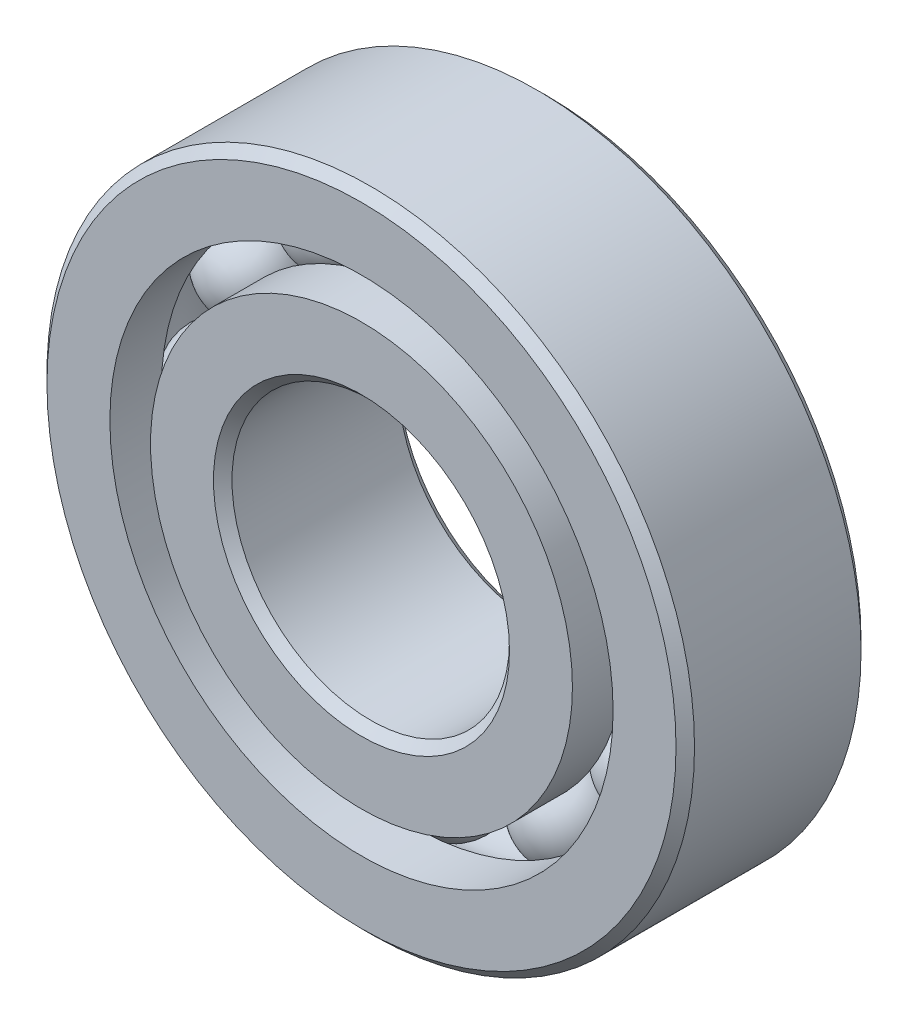
SolidWorks part; units mm, degrees
ref_plane "Front Plane" through (0, 0, 0) normal (0, 0, 1) x (1, 0, 0)
ref_plane "Top Plane" through (0, 0, 0) normal (0, 1, 0) x (1, 0, 0)
ref_plane "Right Plane" through (0, 0, 0) normal (1, 0, 0) x (0, 0, -1)
sketch "Sketch1" plane through (0, 0, 0) normal (1, 0, 0) x (0, 0, -1)
  line L0 (-4, 0) -> (4, 0) construction
  line L1 (0, 14) -> (0, -14) construction
  line L2 (3.6, 14) -> (-3.6, 14)
  line L3 (-3.6, 14) -> (-4, 13.6)
  line L4 (-4, 13.6) -> (-4, 10.8791)
  line L5 (-4, 10.8791) -> (-1.7778, 10.8791)
  line L6 (4, 10.8791) -> (1.7778, 10.8791)
  line L7 (4, 13.6) -> (4, 10.8791)
  line L8 (3.6, 14) -> (4, 13.6)
  line L9 (0, 14) -> (0, 10) construction
  line L10 (0, 10) -> (0, 6) construction
  arc A0 (-1.7778, 10.8791) -> (1.7778, 10.8791) centre (0, 10) cw
  point P14 (0, 6)
  dimension "Width" = 8
  dimension "OD" = 28
  dimension "D1" = 45
  dimension "D2" = 0.4
  dimension "Shaft Dia" = 12
  dimension "D3" = 3.5556
  dimension "D4" = 0.8791
revolve "Revolve1" add sketch "Sketch1" angle 360 about L0
sketch "Sketch3" plane through (0, 0, 0) normal (1, 0, 0) x (0, 0, -1)
  line L0 (-4, 9.1209) -> (-1.7778, 9.1209)
  line L1 (0, 14) -> (0, -14) construction
  line L2 (-4, 13.6) -> (-4, 10.8791) construction
  line L3 (-4, 9.1209) -> (-4, 6.4)
  line L4 (-3.6, 14) -> (-4, 13.6) construction
  line L5 (-4, 6.4) -> (-3.6, 6)
  line L6 (-3.6, 6) -> (3.6, 6)
  line L7 (3.6, 14) -> (3.6, -14) construction
  line L8 (3.6, 6) -> (4, 6.4)
  line L9 (4, -13.6) -> (4, 13.6) construction
  line L10 (4, 6.4) -> (4, 9.1209)
  line L11 (4, 9.1209) -> (1.7778, 9.1209)
  line L13 (3.6, 14) -> (4, 13.6) construction
  arc A0 (1.7778, 10.8791) -> (-1.7778, 10.8791) centre (0, 10) ccw construction
  arc A1 (1.7778, 9.1209) -> (-1.7778, 9.1209) centre (0, 10) cw
revolve "Revolve3" add sketch "Sketch3" angle 360 about L0
sketch "Sketch4" plane through (0, 0, 0) normal (1, 0, 0) x (0, 0, -1)
  line L0 (-1.9833, 10) -> (1.9833, 10)
  arc A2 (-1.9833, 10) -> (1.9833, 10) centre (0, 10) cw
  arc A3 (1.7778, 10.8791) -> (-1.7778, 10.8791) centre (0, 10) ccw construction
revolve "Revolve4" add sketch "Sketch4" angle 360 about L0
ref_axis "Axis1" through (0, 0, -4) along (0, 0, 1)
pattern_circular "CirPattern1" count 12 every 30 about axis through (0, 0, -4) along (0, 0, 1) of bodies 104
sketch "Sketch5" plane through (0, 0, 0) normal (1, 0, 0) x (0, 0, -1)
  line L0 (-4, 10.8791) -> (-1.7778, 10.8791) construction
  line L1 (-3.8, 10.8791) -> (-1.9833, 10.8791)
  line L2 (-3.8, 10.8791) -> (-3.8, 9.1209)
  line L3 (-3.8, 9.1209) -> (-1.9833, 9.1209)
  line L4 (-1.9833, 10.8791) -> (-1.9833, 9.1209)
  line L5 (-4, 9.1209) -> (-1.7778, 9.1209) construction
  line L6 (4, 10.8791) -> (1.7778, 10.8791) construction
  line L7 (3.8, 10.8791) -> (1.9833, 10.8791)
  line L8 (3.8, 10.8791) -> (3.8, 9.1209)
  line L9 (3.8, 9.1209) -> (1.9833, 9.1209)
  line L10 (1.9833, 10.8791) -> (1.9833, 9.1209)
  line L11 (4, 9.1209) -> (1.7778, 9.1209) construction
  line L12 (-3.6, 14) -> (-4, 13.6) construction
  point P18 (-3.8, 13.8)
equation "\"D2@Sketch1\" = \"Width@Sketch1\"*.05"
equation "\"D3@Sketch1\" = \"Width@Sketch1\"/2.25"
equation "\"D4@Sketch1\" = (((\"OD@Sketch1\"-\"Width@Sketch1\")/2)/3.25)/3.5"
equation "\"D2@CirPattern1\" = 360/\"Balls@CirPattern1\""
